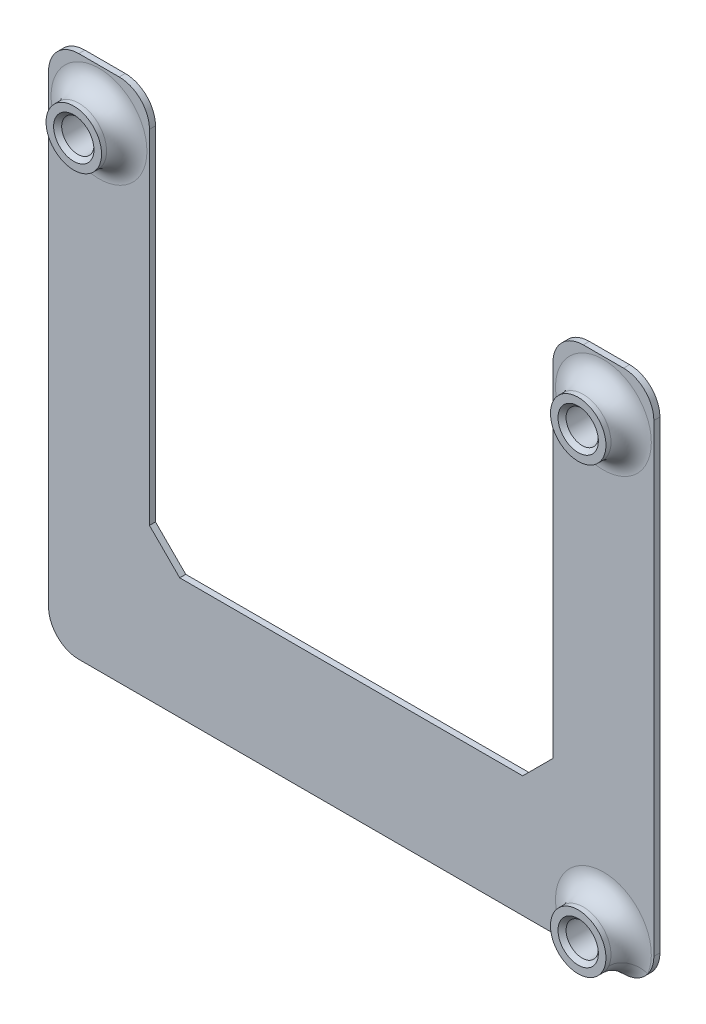
SolidWorks part; units mm, degrees
ref_plane "前视基准面" through (0, 0, 0) normal (0, 0, 1) x (1, 0, 0)
ref_plane "上视基准面" through (0, 0, 0) normal (0, 1, 0) x (1, 0, 0)
ref_plane "右视基准面" through (0, 0, 0) normal (1, 0, 0) x (0, 0, -1)
sketch "草图1" plane through (0, 0, 0) normal (0, 0, 1) x (1, 0, 0)
  line L0 (20, 26) -> (30, 26)
  line L1 (-30, 26) -> (-20, 26)
  line L2 (-30, 26) -> (-30, -26)
  line L3 (-30, -26) -> (30, -26)
  line L4 (30, 26) -> (30, -26)
  line L6 (-20, 26) -> (-20, -11)
  line L7 (-17, -14) -> (17, -14)
  line L8 (20, 26) -> (20, -11)
  line L9 (-20, -11) -> (-17, -14)
  line L10 (17, -14) -> (20, -11)
  circle A0 centre (-25, 21) radius 1.6
  circle A1 centre (25, 21) radius 1.6
  circle A2 centre (25, -23) radius 1.6
  point P5 (20, -14)
  point P6 (-20, -14)
  point P10 (-30, 0)
  point P15 (0, -26)
  dimension "D5" = 3.2
  dimension "D1" = 40
  dimension "D2" = 60
  dimension "D3" = 12
  dimension "D4" = 10
  dimension "D6" = 5
  dimension "D7" = 5
  dimension "D8" = 5
  dimension "D9" = 3
  dimension "D10" = 40
  dimension "D11" = 5
extrude "凸台-拉伸1" add sketch "草图1" along normal blind 0.6
fillet "圆角1" radius 3 6 edges at (30, -26, 0.3) (-30, -26, 0.3) (-30, 26, 0.3) (30, 26, 0.3) (20, 26, 0.3) (-20, 26, 0.3)
sketch "草图3" plane through (0, 0, 0.6) normal (0, 0, 1) x (1, 0, 0)
  circle A0 centre (-25, 21) radius 2.75
  circle A1 centre (25, 21) radius 2.75
  circle A2 centre (25, -23) radius 2.75
  circle A3 centre (25, -23) radius 1.6 construction
  circle A4 centre (25, 21) radius 1.6 construction
  circle A5 centre (-25, 21) radius 1.6 construction
  circle A6 centre (25, -23) radius 1.6
  circle A7 centre (25, 21) radius 1.6
  circle A8 centre (-25, 21) radius 1.6
  dimension "D1" = 5.5
extrude "凸台-拉伸2" add sketch "草图3" along normal blind 2.5
fillet "圆角2" radius 2 3 edges at (27.75, -23, 0.6) (27.75, 21, 0.6) (-22.25, 21, 0.6)
chamfer "倒角1" distance 0.4 angle 45 6 edges at (26.6, -23, 3.1) (26.6, -23, 0) (-23.4, 21, 3.1) (26.6, 21, 3.1) (26.6, 21, 0) (-23.4, 21, 0)
